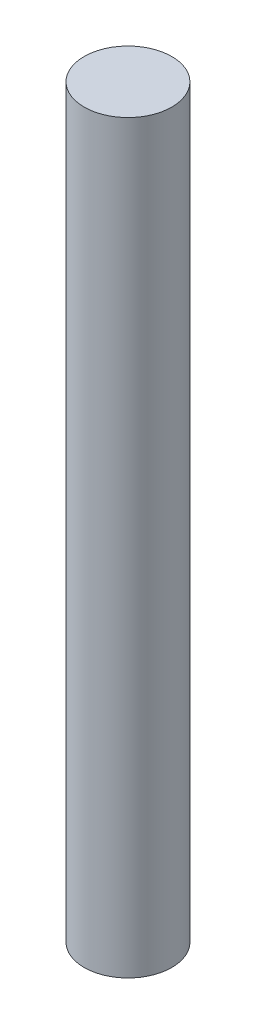
SolidWorks part; units mm, degrees
ref_plane "Front Plane" through (0, 0, 0) normal (0, 0, 1) x (1, 0, 0)
ref_plane "Top Plane" through (0, 0, 0) normal (0, 1, 0) x (1, 0, 0)
ref_plane "Right Plane" through (0, 0, 0) normal (1, 0, 0) x (0, 0, -1)
sketch "Sketch1" plane through (0, 0, 0) normal (0, 1, 0) x (1, 0, 0)
  circle A0 centre (0, 0) radius 5
extrude "Boss-Extrude1" add sketch "Sketch1" along normal blind 85
